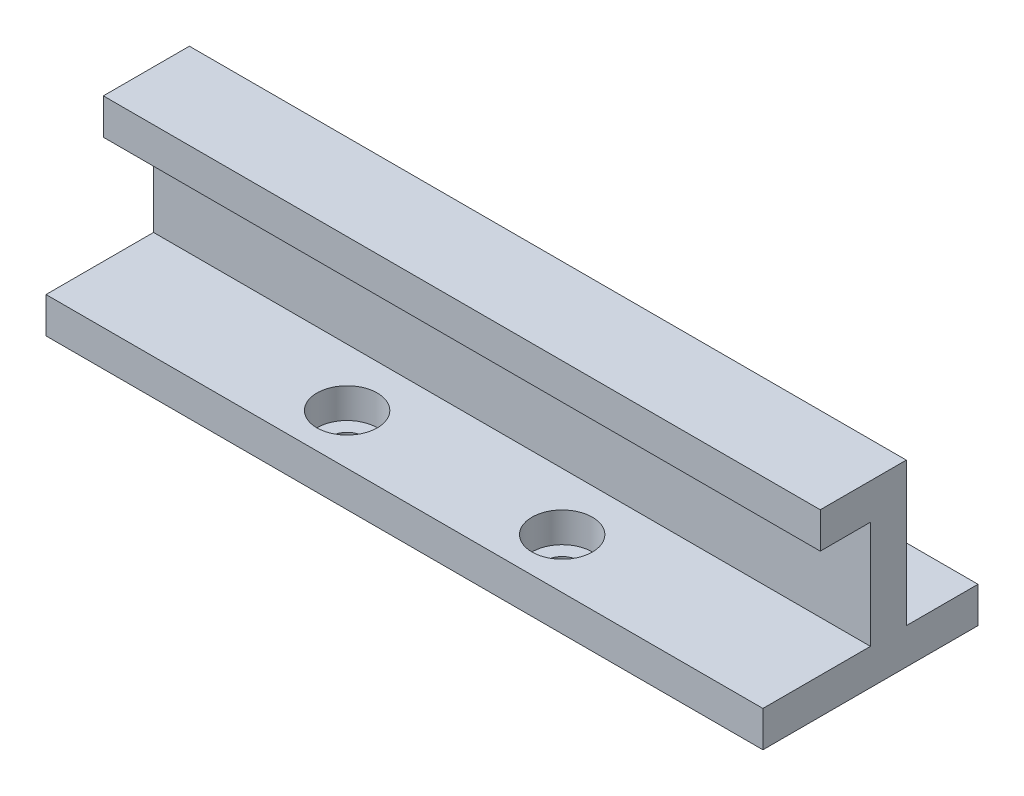
SolidWorks part; units mm, degrees
ref_plane "Front Plane" through (0, 0, 0) normal (0, 0, 1) x (1, 0, 0)
ref_plane "Top Plane" through (0, 0, 0) normal (0, 1, 0) x (1, 0, 0)
ref_plane "Right Plane" through (0, 0, 0) normal (1, 0, 0) x (0, 0, -1)
sketch "Sketch1" plane through (0, 0, 0) normal (0, 1, 0) x (1, 0, 0)
  line L0 (50, 20) -> (50, 0) construction
  line L1 (0, 0) -> (100, 0)
  line L2 (0, 0) -> (0, 20)
  line L3 (0, 20) -> (100, 20)
  line L4 (100, 0) -> (100, 20)
  circle A0 centre (35, 7) radius 2.2
  circle A1 centre (65, 7) radius 2.2
  dimension "D3" = 4.4
  dimension "D4" = 4.4
  dimension "D1" = 20
  dimension "D2" = 100
  dimension "D5" = 7
  dimension "D6" = 7
  dimension "D7" = 30
  dimension "D8" = 15
extrude "Extrude-Base" add sketch "Sketch1" along normal blind 5
sketch "Sketch2" plane through (0, 5, 0) normal (0, 1, 0) x (1, 0, 0)
  line L0 (100, 0) -> (100, 20) construction
  line L1 (0, 20) -> (100, 20)
  line L2 (0, 20) -> (0, 15)
  line L3 (0, 15) -> (100, 15)
  line L4 (100, 20) -> (100, 15)
  dimension "D1" = 5
extrude "Extrude-Vertical clamp" add sketch "Sketch2" along normal blind 20
sketch "Sketch3" plane through (0, 0, -15) normal (0, 0, 1) x (1, 0, 0)
  line L0 (100, 25) -> (100, 5) construction
  line L1 (0, 25) -> (100, 25)
  line L2 (0, 25) -> (0, 20)
  line L3 (0, 20) -> (100, 20)
  line L4 (100, 25) -> (100, 20)
  dimension "D1" = 5
extrude "Extrude-Clamp Roof" add sketch "Sketch3" along normal blind 7
sketch "Sketch5" plane through (0, 0, 0) normal (0, 1, 0) x (1, 0, 0)
  line L0 (100, 20) -> (100, 30)
  line L1 (100, 30) -> (0, 30)
  line L2 (0, 30) -> (0, 20)
  line L3 (0, 20) -> (100, 20)
  line L4 (50, 20) -> (50, 30) construction
  circle A0 centre (70, 25) radius 2.2
  circle A1 centre (30, 25) radius 2.2
  dimension "D6" = 4.4
  dimension "D7" = 4.4
  dimension "D1" = 10
  dimension "D2" = 20
  dimension "D3" = 20
  dimension "D4" = 5
  dimension "D5" = 5
extrude "Boss-Extrude4" add sketch "Sketch5" along normal blind 5
sketch "Sketch4" plane through (0, 5, 0) normal (0, 1, 0) x (1, 0, 0)
  circle A0 centre (35, 7) radius 4.215
  circle A1 centre (65, 7) radius 4.215
  circle A2 centre (35, 7) radius 2.2 construction
  circle A3 centre (65, 7) radius 2.2 construction
  circle A4 centre (30, 25) radius 4.215
  circle A5 centre (70, 25) radius 4.215
  dimension "D1" = 8.43
  dimension "D2" = 8.43
  dimension "D3" = 8.43
  dimension "D4" = 8.43
extrude "Cut-Extrude1" cut sketch "Sketch4" against normal blind 4.2
equation "\"screwInset\"=8.43"
equation "\"D1@Sketch4\"=\"screwInset\""
equation "\"D2@Sketch4\"=\"screwInset\""
equation "\"D3@Sketch4\"=\"screwInset\""
equation "\"D4@Sketch4\"=\"screwInset\""
equation "\"hole_bolt\"=4.4"
equation "\"D3@Sketch1\"=\"hole_bolt\""
equation "\"D4@Sketch1\"=\"hole_bolt\""
equation "\"D7@Sketch5\"=\"hole_bolt\""
equation "\"D6@Sketch5\"=\"hole_bolt\""
